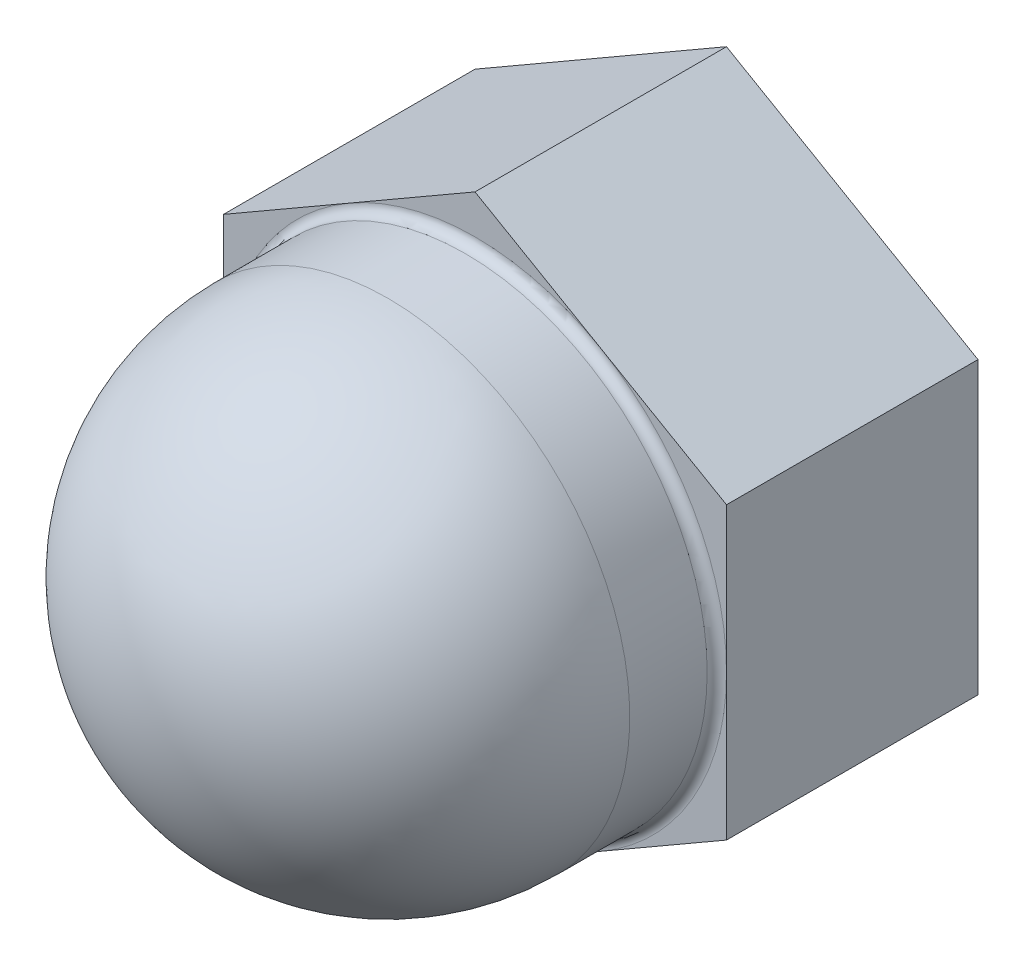
SolidWorks part; units mm, degrees
material "1.0070 (E360)"
ref_plane "Спереди" through (0, 0, 0) normal (0, 0, 1) x (1, 0, 0)
ref_plane "Сверху" through (0, 0, 0) normal (0, 1, 0) x (1, 0, 0)
ref_plane "Справа" through (0, 0, 0) normal (1, 0, 0) x (0, 0, -1)
sketch "Эскиз2" plane through (0, 0, 0) normal (0, 0, 1) x (1, 0, 0)
  line L1 (0, 7.5056) -> (-6.5, 3.7528)
  line L2 (-6.5, 3.7528) -> (-6.5, -3.7528)
  line L3 (-6.5, -3.7528) -> (0, -7.5056)
  line L4 (0, -7.5056) -> (6.5, -3.7528)
  line L5 (6.5, -3.7528) -> (6.5, 3.7528)
  line L6 (6.5, 3.7528) -> (0, 7.5056)
  circle A0 centre (0, 0) radius 6.5 construction
  dimension "D1" = 13
extrude "Бобышка-Вытянуть1" add sketch "Эскиз2" along normal mid plane 6.5
sketch "Эскиз3" plane through (0, 0, 0) normal (1, 0, 0) x (0, 0, -1)
  line L0 (-3.25, 0) -> (-11.75, 0)
  line L1 (-3.25, -3.7528) -> (-3.25, 3.7528) construction
  line L2 (-3.25, 6.25) -> (-3.25, 0)
  line L4 (3.25, -3.7528) -> (3.25, 3.7528) construction
  line L5 (-5.5, 6.25) -> (-3.25, 6.25)
  line L6 (-3.25, 3.7528) -> (-3.25, 7.5056) construction
  arc A0 (-5.5, 6.25) -> (-11.75, 0) centre (-5.5, 0) ccw
  point P8 (-3.25, 6.1856)
  dimension "D2" = 12.5
  dimension "D1" = 15
revolve "Повернуть1" add sketch "Эскиз3" angle 360 about L0
fillet "Скругление1" radius 0.25 1 edges at (0, 6.25, 3.25)
sketch "Эскиз4" plane through (0, 0, -3.25) normal (0, 0, -1) x (-1, 0, 0)
  circle A0 centre (0, 0) radius 4
  dimension "D1" = 8
extrude "Вырез-Вытянуть1" cut sketch "Эскиз4" against normal blind 10.65
thread "Резьба1" pitch 1.25 method extrude profile "Профиль резьбы1" start angle 0, offset 0, length 0, pitch 1.25, diameter 8
ref_plane "Плоскость1" through (4, 0, -3.25) normal (0, 1, 0) x (-1, 0, 0)
sketch "Профиль резьбы1" plane through (4, 0, -3.25) normal (0, 1, 0) x (-1, 0, 0)
  line L0 (0, 0) -> (0, 1.25) construction
  line L1 (0, 0) -> (0.6766, 0.3906)
  line L2 (0.6766, 0.3906) -> (0.6766, 0.5469)
  line L3 (0.6766, 0.5469) -> (0, 0.9375)
  line L4 (0.6766, 0.4687) -> (0, 0.4687) construction
  line L11 (0, 0) -> (0, 0.9375)
  point P2 (0, 0)
  dimension "Pitch" = 1.25
  dimension "Profile_Angle" = 60
  dimension "Profile_Land" = 0.1562
  dimension "Profile_Height" = 0.6766
